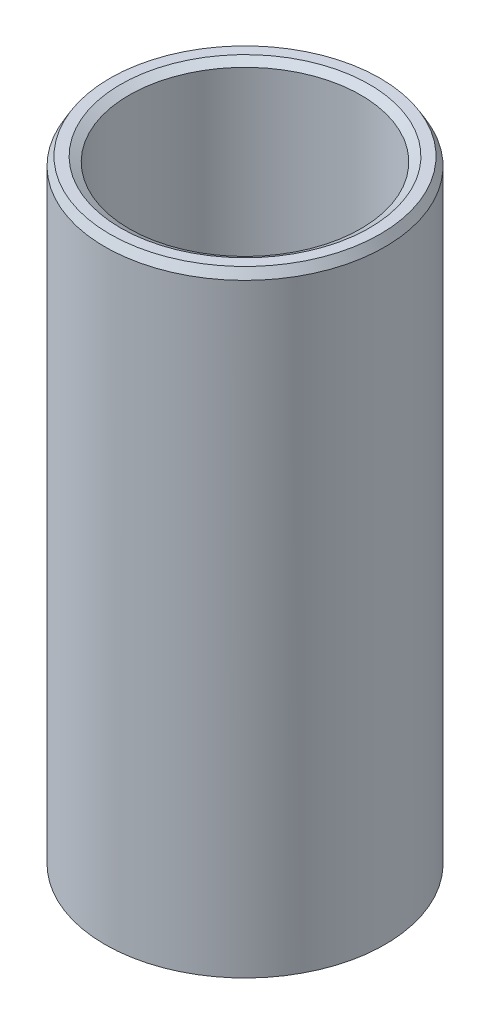
SolidWorks part; units mm, degrees
ref_plane "Front Plane" through (0, 0, 0) normal (0, 0, 1) x (1, 0, 0)
ref_plane "Top Plane" through (0, 0, 0) normal (0, 1, 0) x (1, 0, 0)
ref_plane "Right Plane" through (0, 0, 0) normal (1, 0, 0) x (0, 0, -1)
sketch "Sketch1" plane through (0, 0, 0) normal (0, 1, 0) x (1, 0, 0)
  circle A0 centre (0, 0) radius 45
  dimension "SLEEVE_OD" = 90
extrude "Boss-Extrude1" add sketch "Sketch1" along normal blind 198.4797
sketch "Sketch2" plane through (0, 0, 0) normal (0, 1, 0) x (1, 0, 0)
  circle A0 centre (0, 0) radius 37.2239
  dimension "BORE_D" = 74.4478
extrude "Cut-Extrude1" cut sketch "Sketch2" along normal through all
chamfer "Chamfer1" distance 2.7525 angle 30 4 edges at (0, 198.4797, 37.2239) (0, 0, 37.2239) (0, 0, 45) (0, 198.4797, 45) first distance on face at (0, 198.4797, 37.2239) first distance on face at (0, 0, 37.2239) first distance on face at (0, 198.4797, 45)
